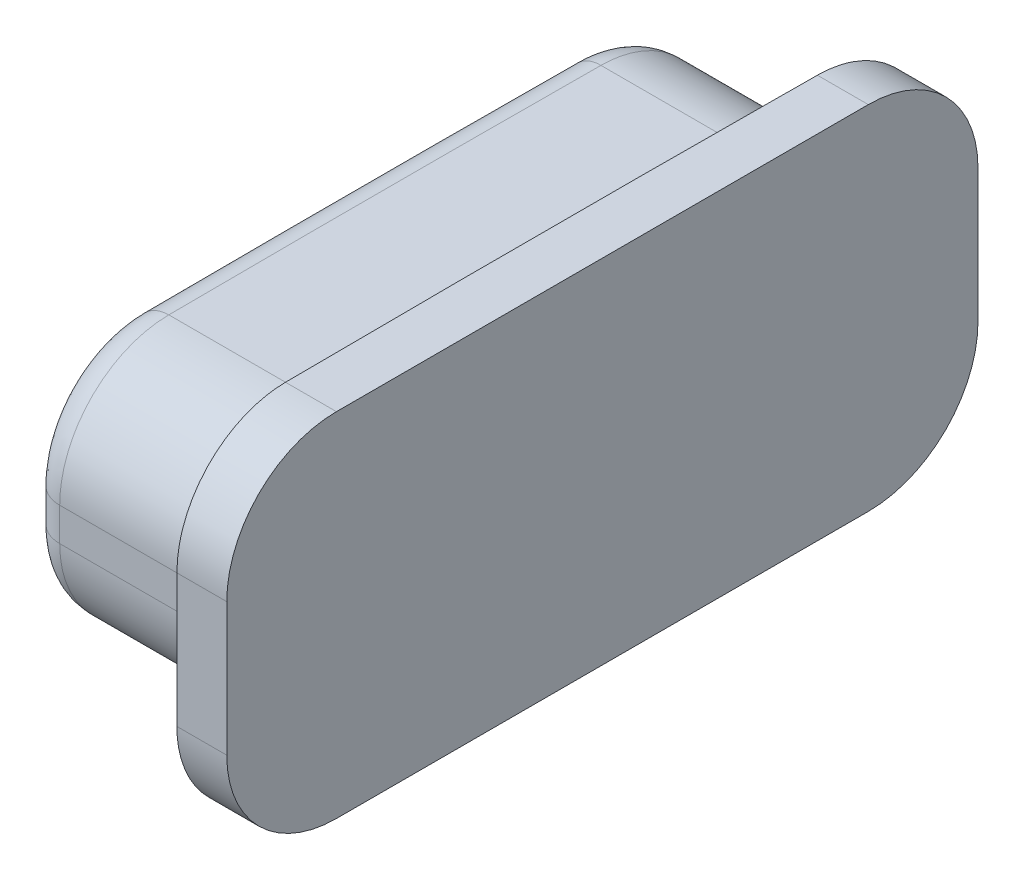
SolidWorks part; units mm, degrees
ref_plane "Front Plane" through (0, 0, 0) normal (0, 0, 1) x (1, 0, 0)
ref_plane "Top Plane" through (0, 0, 0) normal (0, 1, 0) x (1, 0, 0)
ref_plane "Right Plane" through (0, 0, 0) normal (1, 0, 0) x (0, 0, -1)
sketch "Sketch1" plane through (0, 0, 0) normal (0, 1, 0) x (1, 0, 0)
  line L0 (0, 0) -> (-20.8, 0) construction
  line L1 (0, 0) -> (780.6598, 0) construction
  line L2 (-19.8, 21.6348) -> (-19.8, -21.6348) construction
  line L3 (-20.776, 4.9) -> (-17.7759, 4.9)
  line L4 (-17.7679, 5.65) -> (-17.0179, 5.65)
  line L5 (-20.776, -4.9) -> (-17.7759, -4.9)
  line L6 (-17.7679, -5.65) -> (-17.0179, -5.65)
  line L7 (-17.0179, 5.65) -> (-17.0179, -5.65)
  circle A1 centre (480.2, 0) radius 500 construction
  arc A2 (-17.7679, 5.65) -> (-17.7759, 4.9) centre (480.2, 0) ccw
  arc A3 (-20.776, 4.9) -> (-20.776, -4.9) centre (480.2, 0) ccw
  arc A5 (-17.7759, -4.9) -> (-17.7679, -5.65) centre (480.2, 0) ccw
  point P7 (-19.8, 0)
  dimension "D2" = 1000
  dimension "D3" = 996
  dimension "D4" = 1002
  dimension "D1" = 19.8
  dimension "D6" = 4.9
  dimension "D7" = 0.75
extrude "Boss-Extrude1" add sketch "Sketch1" along normal mid plane 5.3
sketch "Sketch2" plane through (0, 2.65, 0) normal (0, 1, 0) x (1, 0, 0)
  line L0 (-39.3064, 0) -> (601.6204, 0) construction
  line L1 (-17.7759, 4.9) -> (-20.776, 4.9)
  line L2 (-17.7759, -4.9) -> (-20.776, -4.9)
  arc A0 (-17.7759, 4.9) -> (-17.7759, -4.9) centre (480.2, 0) ccw
  arc A2 (-20.776, 4.9) -> (-20.776, -4.9) centre (480.2, 0) ccw
  dimension "D2" = 501
extrude "Cut-Extrude2" cut sketch "Sketch2" against normal blind 0.75
mirror "Mirror1" about plane through (0, 0, 0) normal (0, 1, 0) of "Cut-Extrude2"
fillet "Fillet3" radius 1.65 8 edges at (-17.3929, -2.65, 5.65) (-19.276, -1.9, 4.9) (-17.3929, 2.65, 5.65) (-19.276, 1.9, 4.9) (-17.3929, 2.65, -5.65) (-19.276, 1.9, -4.9) (-17.3929, -2.65, -5.65) (-19.276, -1.9, -4.9)
fillet "Fillet4" radius 0.5 8 edges at (-20.7794, -1.2807, -4.5385) (-20.776, 0, -4.9) (-20.7817, 1.5384, -4.2808) (-20.8, 1.9, 0) (-20.7794, 1.2807, 4.5385) (-20.776, 0, 4.9) (-20.7817, -1.5384, 4.2808) (-20.8, -1.9, 0)
